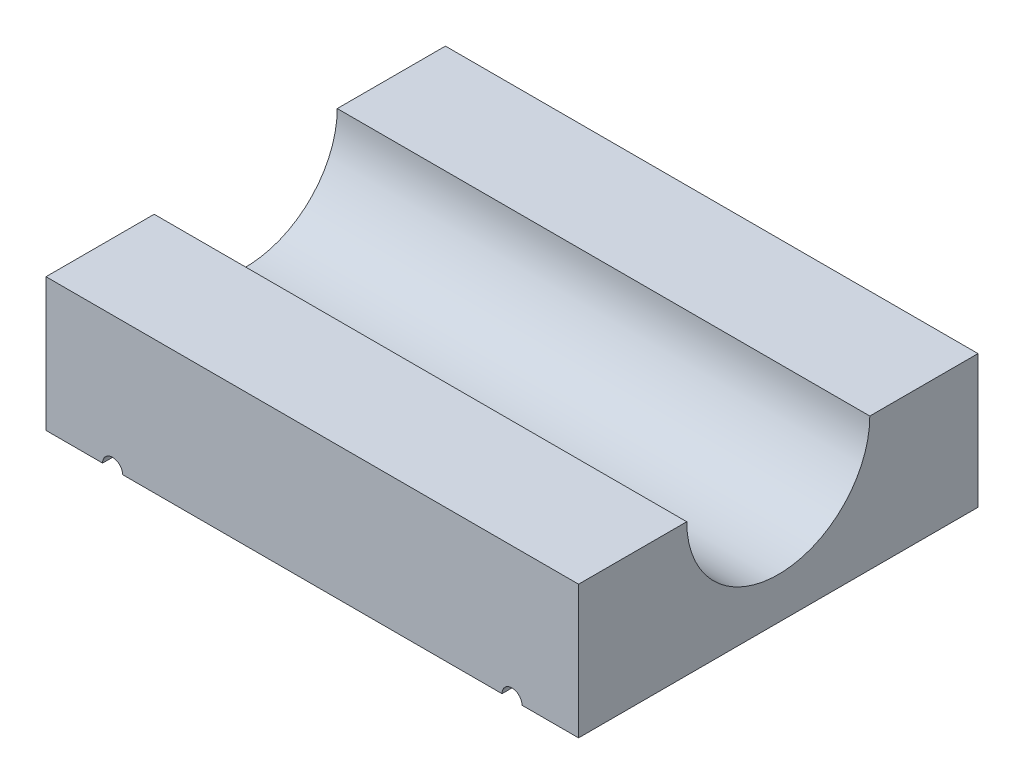
SolidWorks part; units mm, degrees
ref_plane "Front Plane" through (0, 0, 0) normal (0, 0, 1) x (1, 0, 0)
ref_plane "Top Plane" through (0, 0, 0) normal (0, 1, 0) x (1, 0, 0)
ref_plane "Right Plane" through (0, 0, 0) normal (1, 0, 0) x (0, 0, -1)
sketch "Sketch3" plane through (0, 0, 0) normal (1, 0, 0) x (0, 0, -1)
  line L0 (55.5625, 25.4) -> (76.2, 25.4)
  line L1 (0, 0) -> (76.2, 0)
  line L2 (0, 0) -> (0, 25.4)
  line L3 (0, 25.4) -> (20.6375, 25.4)
  line L4 (76.2, 0) -> (76.2, 25.4)
  arc A0 (20.6375, 25.4) -> (55.5625, 25.4) centre (38.1, 25.4) ccw
  point P6 (0, 0)
  point P9 (38.1, 0)
  dimension "D1" = 17.4625
  dimension "D2" = 76.2
  dimension "D3" = 25.4
extrude "Boss-Extrude2" add sketch "Sketch3" along normal blind 101.6
sketch "Sketch4" plane through (0, 0, 0) normal (0, 0, 1) x (1, 0, 0)
  line L0 (101.6, 0) -> (0, 0) construction
  line L1 (0, 25.4) -> (0, 0) construction
  circle A0 centre (12.7, 0) radius 1.905
  circle A1 centre (88.9, 0) radius 1.905
  dimension "D1" = 3.81
  dimension "D2" = 76.2
  dimension "D3" = 12.7
extrude "Cut-Extrude1" cut sketch "Sketch4" against normal through all
